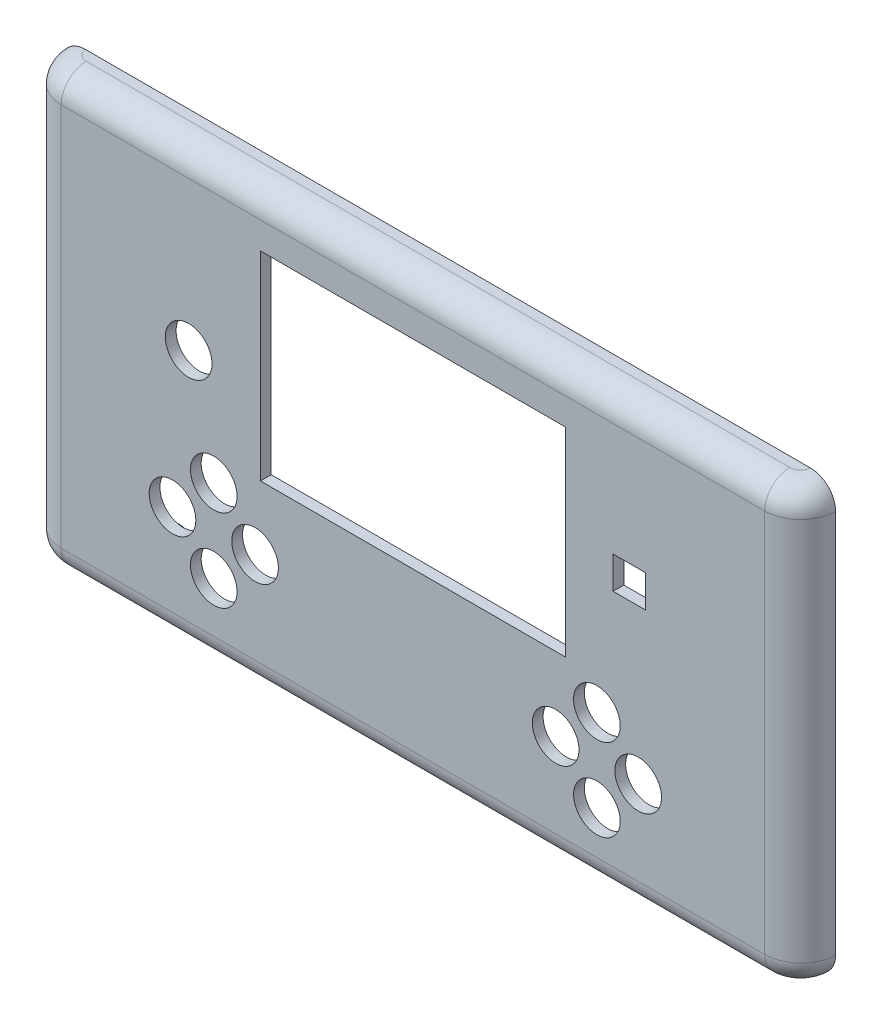
SolidWorks part; units mm, degrees
other "Исправление1"
sketch "Эскиз13" plane through (107.3413, -59.8403, 0) normal (0.0519, -0.0064, -0.9986) x (-0.9976, -0.0462, -0.0516)
ref_plane "Front Plane" through (0, 0, 0) normal (0, 0, 1) x (1, 0, 0)
ref_plane "Top Plane" through (0, 0, 0) normal (0, 1, 0) x (1, 0, 0)
ref_plane "Right Plane" through (0, 0, 0) normal (1, 0, 0) x (0, 0, -1)
sketch "Эскиз1" plane through (0, 0, 0) normal (0, 0, 1) x (1, 0, 0)
  line L0 (0, 57.5) -> (0, -93.1645) construction
  line L1 (-105, 57.5) -> (105, 57.5)
  line L2 (-105, 57.5) -> (-105, -57.5)
  line L3 (-105, -57.5) -> (105, -57.5)
  line L4 (105, 57.5) -> (105, -57.5)
  line L5 (-105, 0) -> (133.2767, 0) construction
  point P10 (0, 0)
  dimension "D1" = 115
  dimension "D2" = 210
extrude "Бобышка-Вытянуть6" add sketch "Эскиз1" along normal blind 6.75
fillet "Скругление6" radius 7 2 edges at (105, 0, 6.75) (-105, 0, 6.75)
fillet "Скругление7" radius 4 6 edges at (102.865, 57.5, 4.7874) (-102.865, 57.5, 4.7874) (-102.865, -57.5, 4.7874) (102.865, -57.5, 4.7874) (0, 57.5, 6.75) (0, -57.5, 6.75)
shell "Оболочка6" thickness 3 removed face at (0, 0, 0) outward yes
sketch "Эскиз10" plane through (0, 0, 9.75) normal (0, 0, 1) x (1, 0, 0)
  line L0 (0, -53.5) -> (0, 53.5) construction
  line L1 (98.0045, 53.5) -> (-98.0045, 53.5) construction
  line L3 (98.0045, -53.5) -> (98.0045, 53.5) construction
  line L4 (-98.0045, 46) -> (98.0045, 46) construction
  line L5 (-98.0045, 53.5) -> (-98.0045, -53.5) construction
  line L6 (42.5, 53.5) -> (42.5, -53.5) construction
  line L7 (-98.0045, -53.5) -> (98.0045, -53.5) construction
  line L8 (-42.5, 53.5) -> (-42.5, -53.5) construction
  line L10 (-42.5, -9.5) -> (42.5, -9.5)
  line L11 (-42.5, -9.5) -> (-42.5, 46)
  line L12 (-42.5, 46) -> (42.5, 46)
  line L13 (42.5, -9.5) -> (42.5, 46)
  point P6 (0, 0)
  point P12 (0, 0)
  dimension "D1" = 55.5
  dimension "D2" = 42.5
  dimension "D3" = 7.5
extrude "Вырез-Вытянуть1" cut sketch "Эскиз10" against normal through all
sketch "Эскиз11" plane through (0, 0, 9.75) normal (0, 0, 1) x (1, 0, 0)
  line L0 (-44, 53.5) -> (-44, -53.5) construction
  line L1 (98.0045, 53.5) -> (-98.0045, 53.5) construction
  line L2 (-98.0045, -53.5) -> (98.0045, -53.5) construction
  line L3 (-42.5, 46) -> (-42.5, -9.5) construction
  line L4 (-42.5, -9.5) -> (-98.0045, -9.5) construction
  line L5 (-98.0045, 53.5) -> (-98.0045, -53.5) construction
  line L6 (-42.5, -9.5) -> (42.5, -9.5) construction
  line L7 (98.0045, -53.5) -> (98.0045, 53.5) construction
  line L8 (-98.0045, -28) -> (98.0045, -28) construction
  line L9 (-98.0045, -39.5) -> (98.0045, -39.5) construction
  line L10 (-55.5, 53.5) -> (-55.5, -53.5) construction
  line L11 (42.5, -9.5) -> (42.5, 46) construction
  line L12 (-62.5, 53.5) -> (-62.5, -53.5) construction
  line L13 (-98.0045, 12) -> (-42.5, 12) construction
  line L14 (55.75, 53.5) -> (55.75, -53.5) construction
  line L15 (64.75, 53.5) -> (64.75, -53.5) construction
  line L16 (42.5, 13) -> (98.0045, 13) construction
  line L17 (42.5, 46) -> (-42.5, 46) construction
  line L18 (42.5, 22) -> (98.0045, 22) construction
  line L20 (64.75, 13) -> (55.75, 13)
  line L21 (64.75, 13) -> (64.75, 22)
  line L22 (64.75, 22) -> (55.75, 22)
  line L23 (55.75, 13) -> (55.75, 22)
  circle A0 centre (-44, -28) radius 6.5
  circle A1 centre (-55.5, -39.5) radius 6.5
  circle A2 centre (-55.5, -16.5) radius 6.5
  circle A3 centre (-67, -28) radius 6.5
  circle A4 centre (51.25, -18.5) radius 6.5
  circle A5 centre (62.75, -30) radius 6.5
  circle A6 centre (51.25, -41.5) radius 6.5
  circle A7 centre (39.75, -30) radius 6.5
  circle A8 centre (-62.5, 12) radius 6.5
  dimension "D3" = 13
  dimension "D6" = 13
  dimension "D12" = 13
  dimension "D1" = 1.5
  dimension "D2" = 18.5
  dimension "D4" = 11.5
  dimension "D5" = 11.5
  dimension "D8" = 20.5
  dimension "D9" = 8.75
  dimension "D10" = 7
  dimension "D11" = 21.5
  dimension "D13" = 4.5
  dimension "D14" = 2
  dimension "D15" = 9
  dimension "D16" = 24
  dimension "D7" = 2
extrude "Вырез-Вытянуть2" cut sketch "Эскиз11" against normal through all
sketch "Эскиз12" plane through (0, 0, 6.75) normal (0, 0, -1) x (-1, 0, 0)
  line L0 (74, 53.5) -> (74, -53.5) construction
  line L1 (-98.0045, 53.5) -> (98.0045, 53.5) construction
  line L2 (98.0045, -53.5) -> (-98.0045, -53.5) construction
  line L3 (42.5, 46) -> (42.5, -9.5) construction
  line L4 (42.5, 37.5) -> (98.0045, 37.5) construction
  line L5 (98.0045, 53.5) -> (98.0045, -53.5) construction
  line L6 (-42.5, 46) -> (42.5, 46) construction
  line L7 (98.0045, -44.75) -> (-98.0045, -44.75) construction
  line L8 (-98.0045, -53.5) -> (-98.0045, 53.5) construction
  line L9 (-68.75, 37.5) -> (-68.75, -53.5) construction
  line L10 (-68.75, 37.5) -> (-68.75, 53.5) construction
  circle A0 centre (74, 37.5) radius 4.5
  circle A1 centre (-68.75, 37.5) radius 4.5
  circle A2 centre (74, -44.75) radius 4.5
  circle A3 centre (-68.75, -44.75) radius 4.5
  circle A4 centre (-68.75, 37.5) radius 1.5
  circle A5 centre (74, 37.5) radius 1.5
  circle A6 centre (74, -44.75) radius 1.5
  circle A7 centre (-68.75, -44.75) radius 1.5
  point P25 (-68.75, 37.5)
  dimension "D3" = 9
  dimension "D7" = 3
  dimension "D8" = 3
  dimension "D9" = 3
  dimension "D10" = 3
  dimension "D1" = 31.5
  dimension "D2" = 8.5
  dimension "D5" = 142.75
  dimension "D6" = 82.25
  dimension "D4" = 2
extrude "Бобышка-Вытянуть9" add sketch "Эскиз12" along normal blind 6
